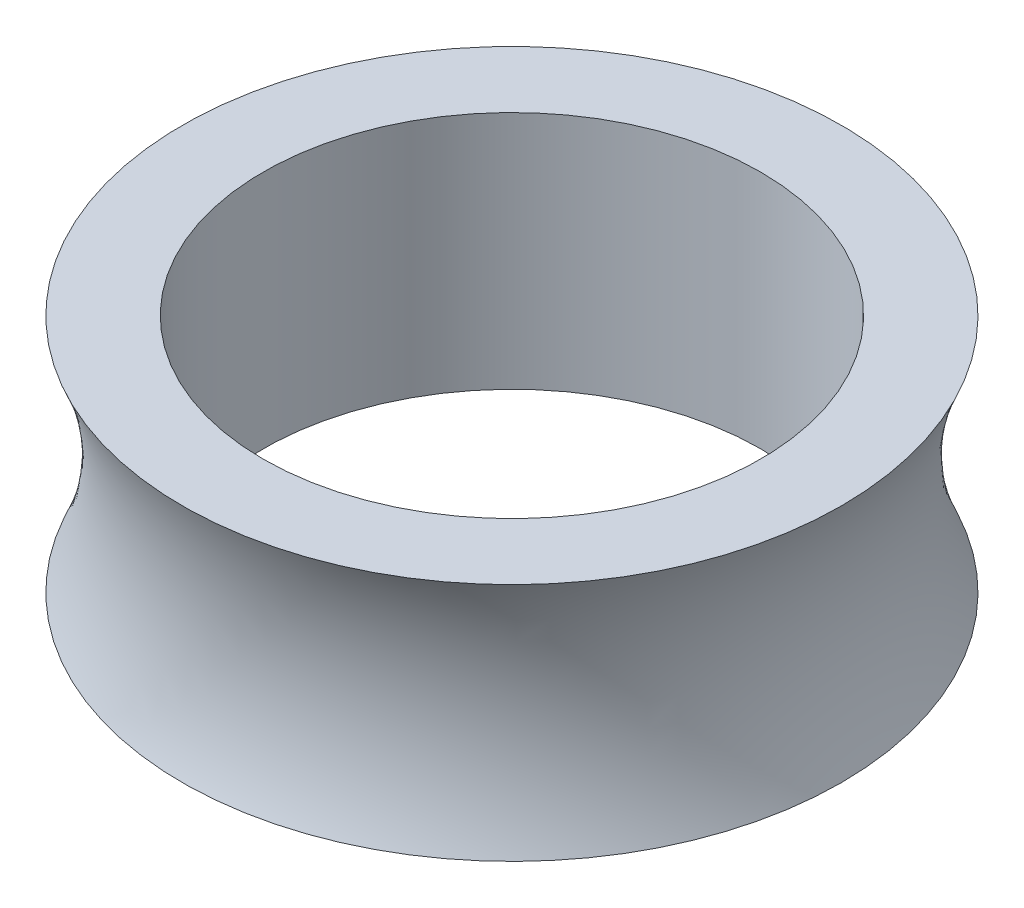
SolidWorks part; units mm, degrees
ref_plane "Front Plane" through (0, 0, 0) normal (0, 0, 1) x (1, 0, 0)
ref_plane "Top Plane" through (0, 0, 0) normal (0, 1, 0) x (1, 0, 0)
ref_plane "Right Plane" through (0, 0, 0) normal (1, 0, 0) x (0, 0, -1)
sketch "Sketch1" plane through (0, 0, 0) normal (0, 1, 0) x (1, 0, 0)
  circle A0 centre (0, 0) radius 5.5
  dimension "D1" = 11
extrude "Boss-Extrude1" add sketch "Sketch1" along normal blind 4
sketch "Sketch4" plane through (0, 0, 0) normal (0, 1, 0) x (1, 0, 0)
  circle A0 centre (0, 0) radius 4.15
  dimension "D1" = 8.3
extrude "Cut-Extrude3" cut sketch "Sketch4" along normal through all
sketch "Sketch5" plane through (0, 0, 0) normal (0, 0, 1) x (1, 0, 0)
  line L0 (5.5, 4) -> (5.5, 0)
  line L1 (5.5, 0) -> (5.5, 4) construction
  arc A0 (5.5, 4) -> (5.5, 0) centre (9.9135, 2) ccw
sweep "Cut-Sweep1" cut profiles "Sketch5" path "Sketch1<2>"
sketch "Sketch1<2>" plane through (0, 0, 0) normal (0, 1, 0) x (1, 0, 0) same geometry as "Sketch1"
